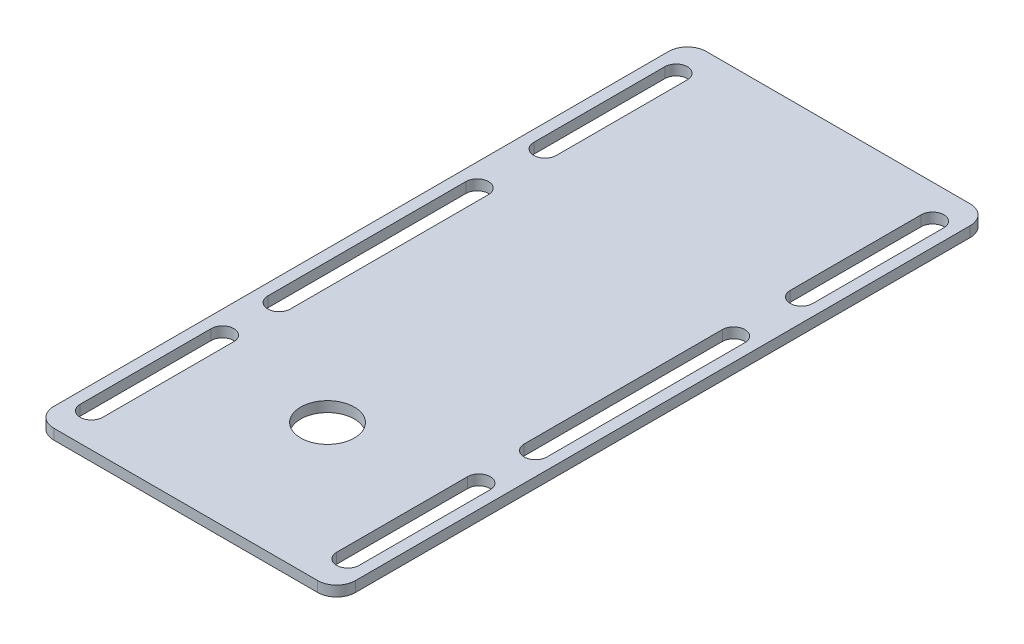
SolidWorks part; units mm, degrees
ref_plane "Front Plane" through (0, 0, 0) normal (0, 0, 1) x (1, 0, 0)
ref_plane "Top Plane" through (0, 0, 0) normal (0, 1, 0) x (1, 0, 0)
ref_plane "Right Plane" through (0, 0, 0) normal (1, 0, 0) x (0, 0, -1)
sketch "Sketch1" plane through (0, 0, 0) normal (0, 1, 0) x (1, 0, 0)
  line L0 (34, 77.5187) -> (34, 42.7687) construction
  line L1 (-35, 86.5188) -> (35, 86.5188)
  line L2 (-40, 81.5187) -> (-40, -81.5187)
  line L3 (-35, -86.5187) -> (35, -86.5187)
  line L4 (40, 81.5187) -> (40, -81.5187)
  line L5 (-40, 86.5188) -> (40, -86.5187) construction
  line L6 (-40, -86.5187) -> (40, 86.5188) construction
  line L7 (37, 77.5187) -> (37, 42.7687)
  line L8 (31, 77.5187) -> (31, 42.7687)
  line L9 (-40, 0) -> (40, 0) construction
  line L10 (0, 86.5188) -> (0, -86.5187) construction
  line L11 (-34, 77.5187) -> (-34, 42.7687) construction
  line L12 (-37, 77.5187) -> (-37, 42.7687)
  line L13 (-31, 77.5187) -> (-31, 42.7687)
  line L14 (34, -77.5187) -> (34, -42.7687) construction
  line L15 (37, -77.5187) -> (37, -42.7687)
  line L16 (31, -77.5187) -> (31, -42.7687)
  line L17 (-34, -77.5187) -> (-34, -42.7687) construction
  line L18 (-37, -77.5187) -> (-37, -42.7687)
  line L19 (-31, -77.5187) -> (-31, -42.7687)
  line L20 (34, 24.7687) -> (34, -27.7687) construction
  line L21 (37, 24.7687) -> (37, -27.7687)
  line L22 (31, 24.7687) -> (31, -27.7687)
  line L23 (-34, 24.7687) -> (-34, -27.7687) construction
  line L24 (-37, 24.7687) -> (-37, -27.7687)
  line L25 (-31, 24.7687) -> (-31, -27.7687)
  arc A0 (-40, -81.5187) -> (-35, -86.5187) centre (-35, -81.5187) ccw
  arc A1 (35, -86.5187) -> (40, -81.5187) centre (35, -81.5187) ccw
  arc A2 (35, 86.5188) -> (40, 81.5187) centre (35, 81.5187) cw
  arc A3 (-35, 86.5188) -> (-40, 81.5187) centre (-35, 81.5187) ccw
  arc A4 (37, 77.5187) -> (31, 77.5187) centre (34, 77.5187) ccw
  arc A5 (31, 42.7687) -> (37, 42.7687) centre (34, 42.7687) ccw
  arc A6 (-37, 77.5187) -> (-31, 77.5187) centre (-34, 77.5187) cw
  arc A7 (-31, 42.7687) -> (-37, 42.7687) centre (-34, 42.7687) cw
  arc A8 (37, -77.5187) -> (31, -77.5187) centre (34, -77.5187) cw
  arc A9 (31, -42.7687) -> (37, -42.7687) centre (34, -42.7687) cw
  arc A10 (-37, -77.5187) -> (-31, -77.5187) centre (-34, -77.5187) ccw
  arc A11 (-31, -42.7687) -> (-37, -42.7687) centre (-34, -42.7687) ccw
  arc A12 (37, 24.7687) -> (31, 24.7687) centre (34, 24.7687) ccw
  arc A13 (31, -27.7687) -> (37, -27.7687) centre (34, -27.7687) ccw
  arc A14 (-37, 24.7687) -> (-31, 24.7687) centre (-34, 24.7687) cw
  arc A15 (-31, -27.7687) -> (-37, -27.7687) centre (-34, -27.7687) cw
  circle A16 centre (0, -48.9201) radius 7.112
  point P0 (0, 0)
  point P20 (34, 60.1437)
  point P31 (-34, 60.1437)
  point P38 (34, -60.1437)
  point P45 (-34, -60.1437)
  point P52 (34, -1.5)
  point P59 (-34, -1.5)
  dimension "D3" = 5
  dimension "D6" = 6
  dimension "D5" = 40.75
  dimension "D9" = 12
  dimension "D10" = 9
  dimension "D1" = 80
  dimension "D2" = 173.0375
  dimension "D4" = 3
  dimension "D7" = 6
  dimension "D8" = 6
extrude "Boss-Extrude1" add sketch "Sketch1" along normal blind 2.75
sketch "Sketch2" plane through (0, 0, 0) normal (1, 0, 0) x (0, 0, -1)
  line L0 (-66.5187, 254) -> (-75.5187, 146.05)
  line L1 (-86.5187, 89.4829) -> (-86.5187, 186.7974) construction
  point P3 (0, 0)
  point P4 (-21.9339, 254)
  dimension "D1" = 11
  dimension "D2" = 20
  dimension "D3" = 146.05
  dimension "D4" = 254
